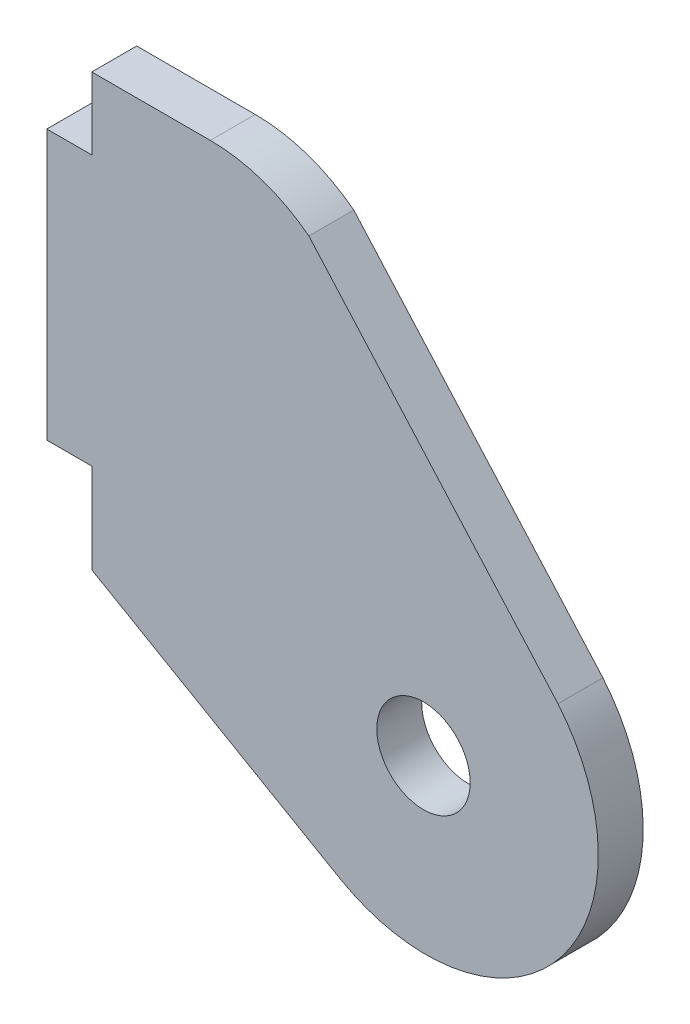
SolidWorks part; units mm, degrees
material "AISI 4130 Steel, annealed at 865C"
ref_plane "X-Y Datum" through (0, 0, 0) normal (0, 0, 1) x (1, 0, 0)
ref_plane "X-Z Datum" through (0, 0, 0) normal (0, 1, 0) x (1, 0, 0)
ref_plane "Y-Z Datum" through (0, 0, 0) normal (1, 0, 0) x (0, 0, -1)
sketch "Sketch1" plane through (0, 0, 0) normal (0, 0, 1) x (1, 0, 0)
  line L8 (-79.4095, -48.8706) -> (-79.4095, -29.8206)
  line L9 (-79.4095, -29.8206) -> (-76.2345, -29.8206)
  line L10 (-76.2345, -29.8206) -> (-76.2345, -24.7406)
  line L11 (-76.2345, -24.7406) -> (-67.8525, -24.7406)
  line L12 (-79.4095, -48.8706) -> (-76.2345, -48.8706)
  line L13 (-76.2345, -48.8706) -> (-76.2345, -55.2206)
  line L14 (-76.2345, -55.2206) -> (-58.7169, -65.3344)
  line L18 (-60.8897, -27.1062) -> (-43.2813, -46.9389)
  arc A2 (-58.7169, -65.3344) -> (-43.2813, -46.9389) centre (-52.6209, -54.7758) ccw
  arc A5 (-67.8525, -24.7406) -> (-60.8897, -27.1062) centre (-67.8525, -36.1706) cw
  dimension "D7" = 12.192
  dimension "D9" = 11.43
  dimension "D1" = 19.05
  dimension "D2" = 5.08
  dimension "D3" = 6.35
  dimension "D4" = 120
  dimension "D5" = 26.7886
  dimension "D8" = 8.382
  dimension "D10" = 37.53
  dimension "D11" = 3.175
  dimension "D12" = 3.175
extrude "Boss-Extrude1" add sketch "Sketch1" along normal blind 3.175
hole_wizard "M6 Clearance Hole1" positions "Sketch2" profile "Sketch3" hole size "M6" standard "ANSI Metric"
sketch "Sketch2" plane through (0, 0, 0) normal (0, 0, -1) x (-1, 0, 0)
  point P4 (52.7858, -54.8788)
sketch "Sketch3" plane through (-52.7858, -54.8788, 0) normal (1, 0, 0) x (0, 1, 0)
  line L0 (0, 0) -> (0, 5.2848)
  line L1 (0, 5.2848) -> (3.3, 3.302)
  line L2 (3.3, 3.302) -> (3.3, 0)
  line L5 (3.3, 0) -> (0, 0)
  line L10 (0, 5.2848) -> (-3.3, 3.302) construction
  line L11 (0, -6.35) -> (0, 107.95) construction
  dimension "Hole Dia." = 6.6
  dimension "Hole Depth" = 3.302
  dimension "Drill Angle" = 118
